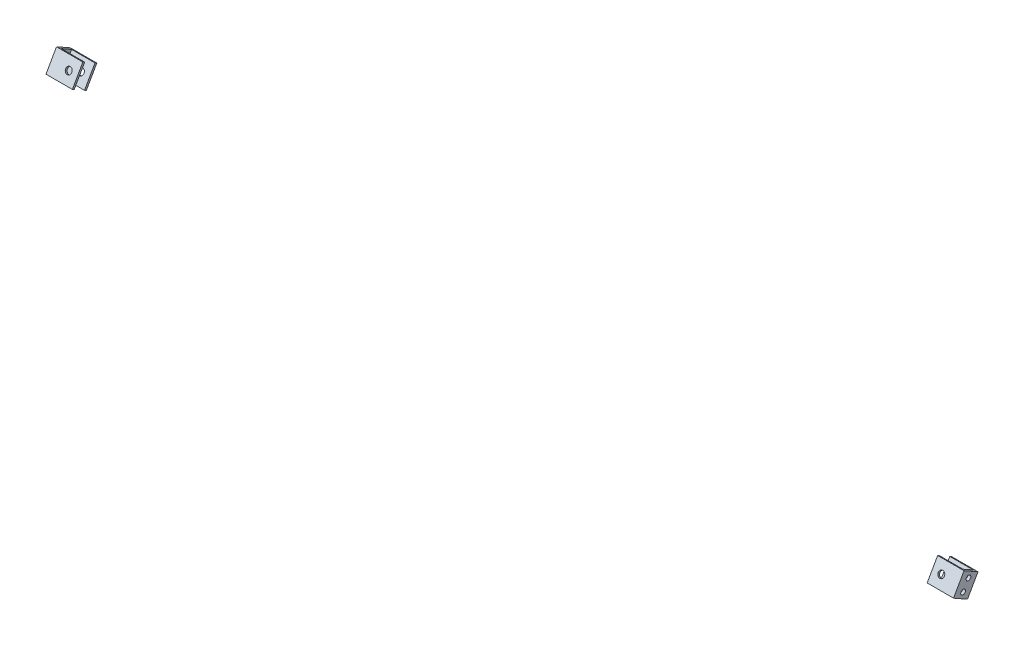
SolidWorks part; units mm, degrees
ref_plane "Front Plane" through (0, 0, 0) normal (0, 0, 1) x (1, 0, 0)
ref_plane "Top Plane" through (0, 0, 0) normal (0, 1, 0) x (1, 0, 0)
ref_plane "Right Plane" through (0, 0, 0) normal (1, 0, 0) x (0, 0, -1)
ref_plane "Plane1" through (0, -217.9452, -384.9482) normal (0, -0.4927, -0.8702) x (-1, 0, 0)
sketch "Sketch1" plane through (0, -217.9452, -384.9482) normal (0, -0.4927, -0.8702) x (-1, 0, 0)
  line L0 (487.45, 1279.1709) -> (468.654, 1279.1709) construction
  line L1 (487.45, 1279.1709) -> (468.654, 1279.1709) construction
  line L2 (487.45, 1290.6009) -> (487.45, 1267.7409)
  line L3 (487.45, 1427.6969) -> (487.45, 1247.6609) construction
  line L4 (487.45, 1290.6009) -> (459.129, 1290.6009)
  line L5 (459.129, 1290.6009) -> (459.129, 1267.7409)
  line L6 (459.129, 1267.7409) -> (487.45, 1267.7409)
  circle A0 centre (468.654, 1279.1709) radius 3.3782
  point P6 (487.45, 1279.1709)
  dimension "D1" = 6.7564
  dimension "D2" = 11.43
  dimension "D3" = 9.525
extrude "Boss-Extrude1" add sketch "Sketch1" along normal mid plane 17.272
sketch "Sketch2" plane through (0, 1103.1987, -624.5954) normal (0, -0.8702, 0.4927) x (1, 0, 0)
  line L0 (-487.45, -442.3632) -> (-459.129, -442.3632) construction
  line L1 (-484.275, -436.0132) -> (-452.4806, -436.0132)
  line L2 (-484.275, -436.0132) -> (-484.275, -448.7132)
  line L3 (-484.275, -448.7132) -> (-452.4806, -448.7132)
  line L4 (-452.4806, -436.0132) -> (-452.4806, -448.7132)
  line L8 (-459.129, -433.7272) -> (-487.45, -433.7272)
  line L9 (-487.45, -433.7272) -> (-487.45, -450.9992)
  line L10 (-487.45, -450.9992) -> (-459.129, -450.9992)
  line L11 (-459.129, -450.9992) -> (-459.129, -433.7272)
  line L12 (-459.129, -433.7272) -> (-487.45, -433.7272) construction
  line L13 (-487.45, -433.7272) -> (-487.45, -450.9992) construction
  line L14 (-487.45, -450.9992) -> (-459.129, -450.9992) construction
  line L15 (-459.129, -450.9992) -> (-459.129, -433.7272) construction
  point P10 (-513.127, -428.9392)
  dimension "D1" = 12.7
  dimension "D3" = 3.175
  dimension "D2" = 0
extrude "Cut-Extrude1" cut sketch "Sketch2" against normal through all
sketch "Sketch3" plane through (-487.45, 0, 0) normal (-1, 0, 0) x (0, 0, 1)
  line L0 (-1020.8064, 905.1465) -> (-1009.5436, 885.2535) construction
  line L1 (-1022.6901, 890.9452) -> (-1007.6599, 899.4548) construction
  line L4 (-1002.0285, 889.5083) -> (-1013.2913, 909.4013)
  line L5 (-1013.2913, 909.4013) -> (-1028.3215, 900.8917)
  line L6 (-1028.3215, 900.8917) -> (-1017.0587, 880.9987)
  line L7 (-1017.0587, 880.9987) -> (-1002.0285, 889.5083)
  line L8 (-1002.0285, 889.5083) -> (-1013.2913, 909.4013) construction
  line L9 (-1013.2913, 909.4013) -> (-1028.3215, 900.8917) construction
  line L10 (-1028.3215, 900.8917) -> (-1017.0587, 880.9987) construction
  line L11 (-1017.0587, 880.9987) -> (-1002.0285, 889.5083) construction
  circle A0 centre (-1018.0658, 900.3059) radius 2.5527
  circle A1 centre (-1012.2842, 890.0941) radius 2.5527
  circle A2 centre (0, 890.8219) radius 2.5527
  dimension "D2" = 5.1054
  dimension "D3" = 5.1054
  dimension "D4" = 5.8674
  dimension "D5" = 5.8674
  dimension "D1" = 0
extrude "Cut-Extrude2" cut sketch "Sketch3" against normal through all
mirror "Mirror2" about plane through (0, 0, 0) normal (1, 0, 0) of bodies 103
